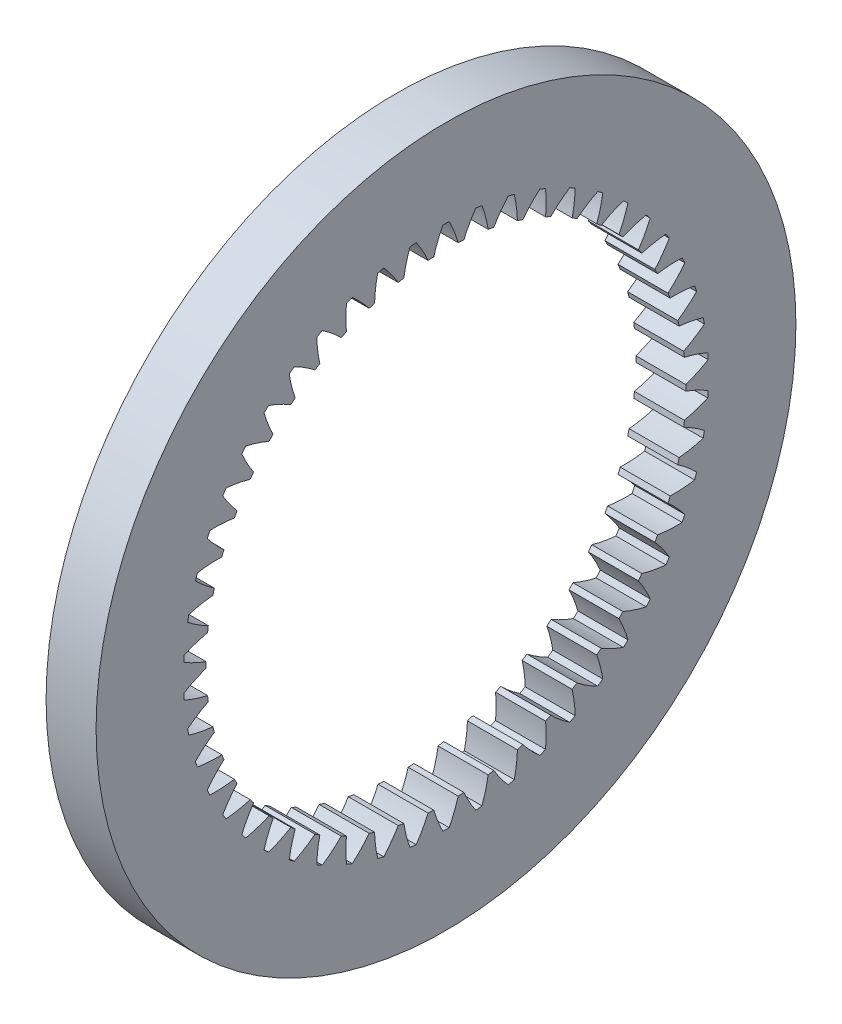
SolidWorks part; units mm, degrees
ref_plane "Plane1" through (0, 0, 0) normal (0, 0, 1) x (1, 0, 0)
ref_plane "Plane2" through (0, 0, 0) normal (0, 1, 0) x (1, 0, 0)
ref_plane "Plane3" through (0, 0, 0) normal (1, 0, 0) x (0, 0, -1)
sketch "HoldingSke" plane through (0, 0, 0) normal (0, 1, 0) x (1, 0, 0)
  line L0 (0, 0) -> (0.6428, -0.766)
  line L1 (-15, 0) -> (100, 0) construction
  line L2 (0, 0) -> (-2.1039, 2.3779)
  line L3 (0, 0) -> (-11.863, 4.5341)
  line L4 (0, 0) -> (5.5511, 6.6156)
  line L5 (0, 0) -> (-23.7986, -8.8762)
  line L6 (0, 0) -> (-10.5278, -7.1032)
  line L7 (-2.1039, 2.3779) -> (3.3635, 27.1825)
  line L8 (-76.2, 3.3779) -> (-54.61, 3.3779)
  line L9 (-71.009, 38.7566) -> (-53.1078, 45.2721)
  line L10 (-76.2, 71.12) -> (104.1128, 71.12)
  line L11 (0, 0) -> (-5, 0)
  line L12 (-76.2, 101.6) -> (-76.162, 101.6)
  line L13 (24.9733, 27.94) -> (52.9518, 28.4284)
  line L14 (24.9733, 27.94) -> (24.9743, 27.94)
  line L15 (24.9733, 27.94) -> (100.4006, 29.5858)
  circle A0 centre (0, 0) radius 35
  circle A1 centre (0, 0) radius 12.7
  circle A2 centre (0, 0) radius 12.7
  dimension "Num_teeth" = 50
  dimension "Pitch_radius" = 180.3128
  dimension "Width" = 5
  dimension "Diameter" = 70
sketch "BasProSke" plane through (0, 0, 0) normal (0, 1, 0) x (1, 0, 0)
  line L0 (-10, 0) -> (60, 0) construction
  line L1 (0, 24) -> (0, 35)
  line L2 (0, 24) -> (5, 24)
  line L3 (5, 24) -> (5, 35)
  line L4 (5, 35) -> (0, 35)
  dimension "Thickness" = 5
  dimension "Diameter" = 70
revolve "Base-Revolve" add sketch "BasProSke" angle 360 about L0
sketch "TooCutSke" plane through (0, 0, 0) normal (1, 0, 0) x (0, 0, -1)
  line L3 (0.8803, 24.9845) -> (0.8803, 53.6633) construction
  line L4 (0, 0) -> (0, 59.563) construction
  line L5 (0, 0) -> (-4.2903, 68.1927) construction
  line L6 (-10.7899, 20.506) -> (36.4405, 23.4775) construction
  circle A0 centre (0, 0) radius 25 construction
  circle A1 centre (0, 0) radius 26.251 construction
  circle A2 centre (0, 0) radius 21.1431 construction
  circle A3 centre (0, 0) radius 23.9746 construction
  arc A4 (1.2282, 23.9431) -> (0.3126, 26.2491) centre (-10.7899, 20.506) ccw
  arc A5 (1.2282, 23.9431) -> (-1.2282, 23.9431) centre (0, 0) ccw
  arc A6 (0.3126, 26.2491) -> (-0.3126, 26.2491) centre (0, 0) ccw
  arc A7 (-0.3126, 26.2491) -> (-1.2282, 23.9431) centre (10.7899, 20.506) ccw
extrude "ToothCut" cut sketch "TooCutSke" along normal through all
fillet "Breaks" [suppressed] radius 0.1
fillet "RootFillets" [suppressed] radius 0.251
pattern_circular "TeethCuts" count 50 every 7.2 about axis through (-10, 0, 0) along (1, 0, 0) of "RootFillets", "Breaks", "ToothCut"
equation "' \"Module@HoldingSke\" = 6.35"
equation "' \"Num_teeth@HoldingSke\" = 24"
equation "' \"Ap@HoldingSke\" =  14.5"
equation "' \"Ap@HoldingSke\" = 14.5"
equation "' \"Width@HoldingSke\" = 12"
equation "' \"Diameter@HoldingSke\" = 8 * 25.4"
equation "' \"Show_teeth@HoldingSke\" = 100"
equation "' \"Backlash@HoldingSke\" = 0.009 * 25.4"
equation "' \"Addendum_fac@HoldingSke\" = 1.0"
equation "' \"Dedendum_fac@HoldingSke\" = 1.25"
equation "' \"Dedendum_add@HoldingSke\" = 0.00005 * 25.4"
equation "' \"Clearance_fac@HoldingSke\" = 0.25"
equation "\"Pitch@HoldingSke\" = 1 / \"Module@HoldingSke\" "
equation "\"Overcut_dia@TooCutSke\" = (\"Num_teeth@HoldingSke\" - 2 * \"Addendum_fac@HoldingSke\") / \"Pitch@HoldingSke\" - 0.002 * 25.4"
equation "\"Pitch_dia@TooCutSke\" = \"Num_teeth@HoldingSke\" / \"Pitch@HoldingSke\""
equation "\"Base_dia@TooCutSke\" = \"Num_teeth@HoldingSke\" / \"Pitch@HoldingSke\" * cos((\"Ap@HoldingSke\"  * 3.14159265 / 180)) * 0.90"
equation "\"Root_dia@TooCutSke\" = \"Num_teeth@HoldingSke\"  / \"Pitch@HoldingSke\" + 2 *  \"Dedendum_fac@HoldingSke\"/ \"Pitch@HoldingSke\" + \"Dedendum_add@HoldingSke\" * 2"
equation "\"Half_ang@TooCutSke\" = 180 / \"Num_teeth@HoldingSke\""
equation "\"Half_CT@TooCutSke\" = \"Num_teeth@HoldingSke\" / \"Pitch@HoldingSke\" * sin((3.14159265 / 2 / \"Num_teeth@HoldingSke\")) / 2 + 10 * \"Backlash@HoldingSke\" / 4"
equation "\"Flank_rad@TooCutSke\" = \"Num_teeth@HoldingSke\" / \"Pitch@HoldingSke\" / 4"
equation "\"Radius@RootFillets\"= \"Clearance_fac@HoldingSke\" / \"Pitch@HoldingSke\" + \"Dedendum_add@HoldingSke\""
equation "\"Break_rad@Breaks\" = 0.02 / \"Pitch@HoldingSke\" * 5"
equation "\"Num_teeth@TeethCuts\" = int( \"Show_teeth@HoldingSke\" ) + 1"
equation "\"Num_teeth@TeethCuts\" = ((sgn( \"Num_teeth@TeethCuts\" - \"Num_teeth@HoldingSke\" )-1)*( \"Num_teeth@TeethCuts\" - \"Num_teeth@HoldingSke\" ))/-2+ \"Num_teeth@HoldingSke\""
equation "\"Num_teeth@TeethCuts\" = ((sgn( \"Num_teeth@TeethCuts\" - 2.0)+1)*( \"Num_teeth@TeethCuts\" - 2.0))/2 +2.0"
equation "\"Angle@TeethCuts\" = 360.0 / \"Num_teeth@HoldingSke\""
equation "\"Diameter@BasProSke\" = \"Num_teeth@HoldingSke\"  / \"Pitch@HoldingSke\" + 2 *  \"Dedendum_fac@HoldingSke\"/ \"Pitch@HoldingSke\" + \"Dedendum_add@HoldingSke\" * 2 + 0.002 * 25.4"
equation "\"Diameter@BasProSke\" = ((sgn( \"Diameter@BasProSke\"  - \"Diameter@HoldingSke\" )+1)*( \"Diameter@BasProSke\"  - \"Diameter@HoldingSke\" ))/2 + \"Diameter@HoldingSke\""
equation "\"Inside_diameter@BasProSke\" =  (\"Num_teeth@HoldingSke\" - 2 * \"Addendum_fac@HoldingSke\") / \"Pitch@HoldingSke\" "
equation "\"Thickness@BasProSke\"  = \"Width@HoldingSke\""
